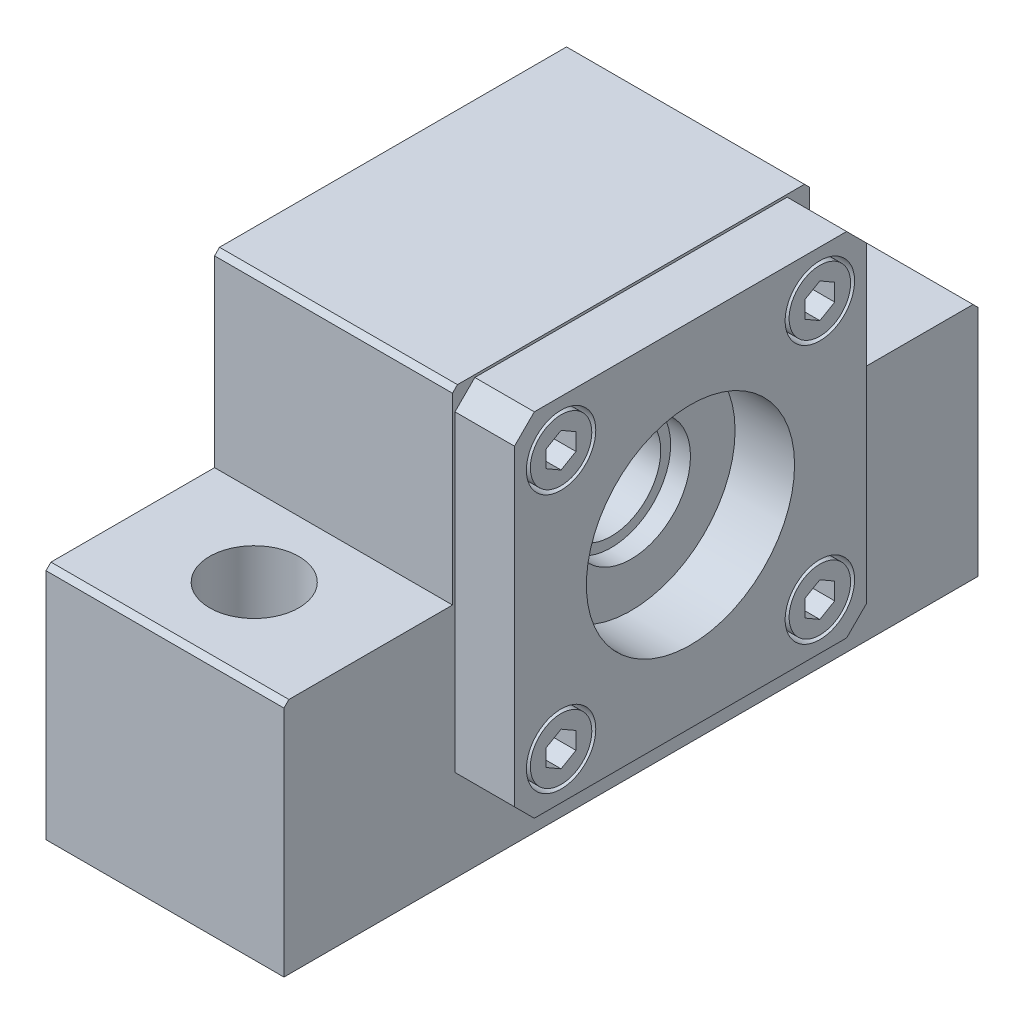
SolidWorks part; units mm, degrees
note: '?' marks a value the reader was unsure of.
ref_plane "Front Plane" through (0, 0, 0) normal (0, 0, 1) x (1, 0, 0)
ref_plane "Top Plane" through (0, 0, 0) normal (0, 1, 0) x (1, 0, 0)
ref_plane "Right Plane" through (0, 0, 0) normal (1, 0, 0) x (0, 0, -1)
ref_axis "Axis_X" through (-1.45, 0, 0) along (1, 0, 0)?
ref_axis "Axis_Y" through (0, 36.525, 0) along (0, -1, 0)?
ref_axis "Axis_Z" through (0, 0, -28.6) along (0, 0, 1)?
sketch "Sketch1" plane through (0, 0, 0) normal (1, 0, 0) x (0, 0, -1)
  line L0 (-18, 42.5) -> (-18, 24)
  line L1 (-17.5, 43) -> (17.5, 43)
  line L2 (-35, 23.5) -> (-35, 0)
  line L3 (-35, 0) -> (35, 0)
  line L4 (35, 23.5) -> (35, 0)
  line L5 (-34.5, 24) -> (-35, 23.5)
  line L6 (34.5, 24) -> (35, 23.5)
  line L7 (-18, 24) -> (-34.5, 24)
  line L8 (18, 42.5) -> (18, 24)
  line L9 (18, 24) -> (34.5, 24)
  line L10 (-18, 42.5) -> (-17.5, 43)
  line L11 (17.5, 43) -> (18, 42.5)
  dimension "B" = 70
  dimension "H" = 43
  dimension "H1" = 24
  dimension "B1" = 36
  dimension "FIX_1" = 45
  dimension "FIX_2" = 0.5
extrude "Boss-Extrude1" add sketch "Sketch1" along normal blind 24
hole_wizard "CBORE1" [suppressed] positions "Sketch3" profile "Sketch2" counterbore size "M4" standard "JIS"
sketch "Sketch3" plane through (0, 26, 0) normal (0, 1, 0) x (1, 0, 0)
  line L0 (11.5, 19) -> (11.5, -19) construction
  line L1 (11.5, 0) -> (0, 0) construction
  point P0 (11.5, 19)
  point P2 (11.5, -19)
  dimension "P" = 52
  dimension "KSS_1" = 12
sketch "Sketch2" plane through (11.5, 26, -19) normal (1, 0, 0) x (0, 0, 1)
  line L0 (0, 0) -> (0, 26)
  line L1 (0, 26) -> (3.3, 26)
  line L3 (3.3, 26) -> (3.3, 12)
  line L4 (3.3, 12) -> (5.5, 12)
  line L5 (5.5, 12) -> (5.5, 0)
  line L7 (5.5, 0) -> (0, 0)
  line L11 (0, -6.35) -> (0, 107.95) construction
  dimension "D1_s" = 9
  dimension "Thru Hole Depth" = 26
  dimension "D2_s" = 11
  dimension "L_s" = 12
sketch "Sketch4" plane through (24, 0, 0) normal (1, 0, 0) x (0, 0, -1)
  line L0 (-17.75, 40.75) -> (-15.75, 42.75)
  line L1 (-15.75, 42.75) -> (15.75, 42.75)
  line L2 (-17.75, 40.75) -> (-17.75, 9.25)
  line L3 (-15.75, 7.25) -> (15.75, 7.25)
  line L4 (17.75, 40.75) -> (17.75, 9.25)
  line L5 (-16.75, 41.75) -> (16.75, 8.25) construction
  line L6 (-16.75, 8.25) -> (16.75, 41.75) construction
  line L7 (15.75, 42.75) -> (17.75, 40.75)
  line L8 (17.75, 9.25) -> (15.75, 7.25)
  line L9 (-17.75, 9.25) -> (-15.75, 7.25)
  line L10 (-13.05, 38.05) -> (-13.05, 11.95) construction
  line L11 (-13.05, 11.95) -> (13.05, 11.95) construction
  line L12 (13.05, 11.95) -> (13.05, 38.05) construction
  line L13 (13.05, 38.05) -> (-13.05, 38.05) construction
  circle A0 centre (-13.05, 38.05) radius 3.5
  circle A1 centre (13.05, 38.05) radius 3.5
  circle A2 centre (-13.05, 11.95) radius 3.5
  circle A3 centre (13.05, 11.95) radius 3.5
  point P0 (0, 25)
  dimension "MSM_2" = 7
  dimension "MSM_11" = 35.5
  dimension "FIX_3" = 2
  dimension "FIX_4" = 45
  dimension "MSM_1" = 4.7
  dimension "H_S" = 25
extrude "Boss-Extrude2" add sketch "Sketch4" along normal blind 6
sketch "Sketch5" plane through (24, 0, 0) normal (1, 0, 0) x (0, 0, -1)
  circle A0 centre (-13.05, 38.05) radius 3.1
  circle A1 centre (13.05, 38.05) radius 3.1
  circle A2 centre (13.05, 11.95) radius 3.1
  circle A3 centre (-13.05, 11.95) radius 3.1
  dimension "MSM_3" = 6.2
extrude "Boss-Extrude3" add sketch "Sketch5" along normal blind 6
hole_wizard "DiameterHole1" positions "Sketch7" profile "Sketch6" hole size "Ø0.15" standard "JIS"
sketch "Sketch7" plane through (30, 0, 0) normal (1, 0, 0) x (0, 0, -1)
  point P0 (-13.05, 38.05)
  point P2 (13.05, 38.05)
  point P4 (-13.05, 11.95)
  point P7 (13.05, 11.95)
sketch "Sketch6" plane through (30, 38.05, 13.05) normal (0, 1, 0) x (0, 0, -1)
  line L0 (0, 0) -> (0, 3.9013)
  line L1 (0, 3.9013) -> (1.5, 3)
  line L2 (1.5, 3) -> (1.5, 0)
  line L5 (1.5, 0) -> (0, 0)
  line L10 (0, 3.9013) -> (-1.5, 3) construction
  line L11 (0, -6.35) -> (0, 107.95) construction
  dimension "HD_1" = 3
  dimension "HL_1" = 3
  dimension "Drill Angle" = 118
sketch "Sketch8" plane through (30, 0, 0) normal (1, 0, 0) x (0, 0, -1)
  line L0 (-13.05, 38.05) -> (-13.05, 11.95) construction
  line L1 (-13.05, 36.3179) -> (-11.55, 37.184)
  line L2 (-11.55, 37.184) -> (-11.55, 38.916)
  line L3 (-11.55, 38.916) -> (-13.05, 39.7821)
  line L4 (-13.05, 39.7821) -> (-14.55, 38.916)
  line L5 (-14.55, 38.916) -> (-14.55, 37.184)
  line L6 (-14.55, 37.184) -> (-13.05, 36.3179)
  line L7 (14.55, 37.184) -> (14.55, 38.916)
  line L8 (14.55, 38.916) -> (13.05, 39.7821)
  line L9 (13.05, 39.7821) -> (11.55, 38.916)
  line L10 (11.55, 38.916) -> (11.55, 37.184)
  line L11 (11.55, 37.184) -> (13.05, 36.3179)
  line L12 (13.05, 36.3179) -> (14.55, 37.184)
  line L13 (-11.55, 11.084) -> (-11.55, 12.816)
  line L14 (-11.55, 12.816) -> (-13.05, 13.6821)
  line L15 (-13.05, 13.6821) -> (-14.55, 12.816)
  line L16 (-14.55, 12.816) -> (-14.55, 11.084)
  line L17 (-14.55, 11.084) -> (-13.05, 10.2179)
  line L18 (-13.05, 10.2179) -> (-11.55, 11.084)
  line L19 (14.55, 11.084) -> (14.55, 12.816)
  line L20 (14.55, 12.816) -> (13.05, 13.6821)
  line L21 (13.05, 13.6821) -> (11.55, 12.816)
  line L22 (11.55, 12.816) -> (11.55, 11.084)
  line L23 (11.55, 11.084) -> (13.05, 10.2179)
  line L24 (13.05, 10.2179) -> (14.55, 11.084)
  line L25 (13.05, 11.95) -> (13.05, 38.05) construction
  circle A0 centre (-13.05, 38.05) radius 1.5 construction
  circle A1 centre (13.05, 38.05) radius 1.5 construction
  circle A2 centre (-13.05, 11.95) radius 1.5 construction
  circle A3 centre (13.05, 11.95) radius 1.5 construction
extrude "Cut-Extrude1" cut sketch "Sketch8" against normal blind 3
sketch "Sketch9" plane through (0, 0, 0) normal (0, 0, 1) x (1, 0, 0)
  line L0 (0, 35.5) -> (3, 35.5)
  line L1 (3, 35.5) -> (3, 31)
  line L2 (3, 31) -> (6, 31)
  line L3 (6, 31) -> (6, 30)
  line L4 (6, 30) -> (22, 30)
  line L5 (22, 30) -> (22, 31)
  line L6 (22, 31) -> (24, 31)
  line L7 (24, 31) -> (24, 35.5)
  line L8 (24, 35.5) -> (30, 35.5)
  line L9 (30, 35.5) -> (30, 25)
  line L10 (30, 25) -> (0, 25) construction
  line L11 (0, 25) -> (0, 35.5)
  line L13 (0, 25) -> (30, 25)
  dimension "MSM_4" = 21
  dimension "MSM_5" = 12
  dimension "D_s" = 10
  dimension "MSM_6" = 3
  dimension "L3" = 6
  dimension "MSM_7" = 16
  dimension "L" = 24
  dimension "L1" = 6
  dimension "H_S" = 25
revolve "Cut-Revolve1" cut sketch "Sketch9" angle 360 about L10
hole_wizard "DiameterHole2" [suppressed] positions "Sketch11" profile "Sketch10" hole size "Ø0.15" standard "JIS"
sketch "Sketch11" plane through (23, 0, 0) normal (1, 0, 0) x (0, 0, -1)
  line L0 (0, 26) -> (-9, 17) construction
  line L1 (-9, 17) -> (0, 8) construction
  line L2 (0, 8) -> (9, 17) construction
  line L3 (9, 17) -> (0, 26) construction
  line L5 (0, 25) -> (0, 17) construction
  line L6 (-9, 17) -> (9, 17) construction
  line L9 (0, 26) -> (0, 8) construction
  line L11 (0, 22) -> (0, 25) construction
  point P0 (0, 26)
  point P2 (-9, 17)
  point P4 (9, 17)
  point P6 (0, 8)
  dimension "MSM_8" = 18
sketch "Sketch10" plane through (23, 26, 0) normal (0, 1, 0) x (0, 0, -1)
  line L0 (0, 0) -> (0, 3.3412)
  line L1 (0, 3.3412) -> (1.4, 2.5)
  line L2 (1.4, 2.5) -> (1.4, 0)
  line L5 (1.4, 0) -> (0, 0)
  line L10 (0, 3.3412) -> (-1.4, 2.5) construction
  line L11 (0, -6.35) -> (0, 107.95) construction
  dimension "HD_2" = 2.8
  dimension "HL_2" = 2.5
  dimension "Drill Angle" = 118
sketch "Sketch12" plane through (0, 0, 0) normal (0, 0, 1) x (1, 0, 0)
  line L0 (24, 37) -> (22, 37)
  line L1 (24, 31) -> (24, 35.5) construction
  line L2 (22, 37) -> (22, 36.45)
  line L3 (22, 36.45) -> (24, 36.45)
  line L5 (0, 25) -> (30, 25) construction
  line L6 (22, 30) -> (22, 31) construction
  line L7 (24, 37) -> (24, 36.45)
  dimension "MSM_9" = 22.9
  dimension "MSM_10" = 24
revolve "Cut-Revolve2" [suppressed] cut sketch "Sketch12" angle 360 about L5
hole_wizard "DiameterHole3" positions "Sketch14" profile "Sketch13" hole size "Ø0.15" standard "JIS" end condition through all
sketch "Sketch14" plane through (0, 24, 0) normal (0, 1, 0) x (1, 0, 0)
  line L0 (12, 26) -> (12, -26) construction
  line L2 (0, 0) -> (12, 0) construction
  point P0 (12, -26)
  point P3 (12, 26)
  dimension "P" = 52
  dimension "KSS_1" = 12
sketch "Sketch13" plane through (12, 24, 26) normal (1, 0, 0) x (0, 0, 1)
  line L0 (0, 0) -> (0, 24)
  line L1 (0, 24) -> (4.5, 24)
  line L2 (4.5, 24) -> (4.5, 0)
  line L5 (4.5, 0) -> (0, 0)
  line L11 (0, -6.35) -> (0, 107.95) construction
  dimension "D1_s" = 9
  dimension "Thru Hole Depth" = 24
equation "\"Factor\"= 1.082532"
equation "\"KSS_1\"= \"L@Boss-Extrude1\" / 2"
